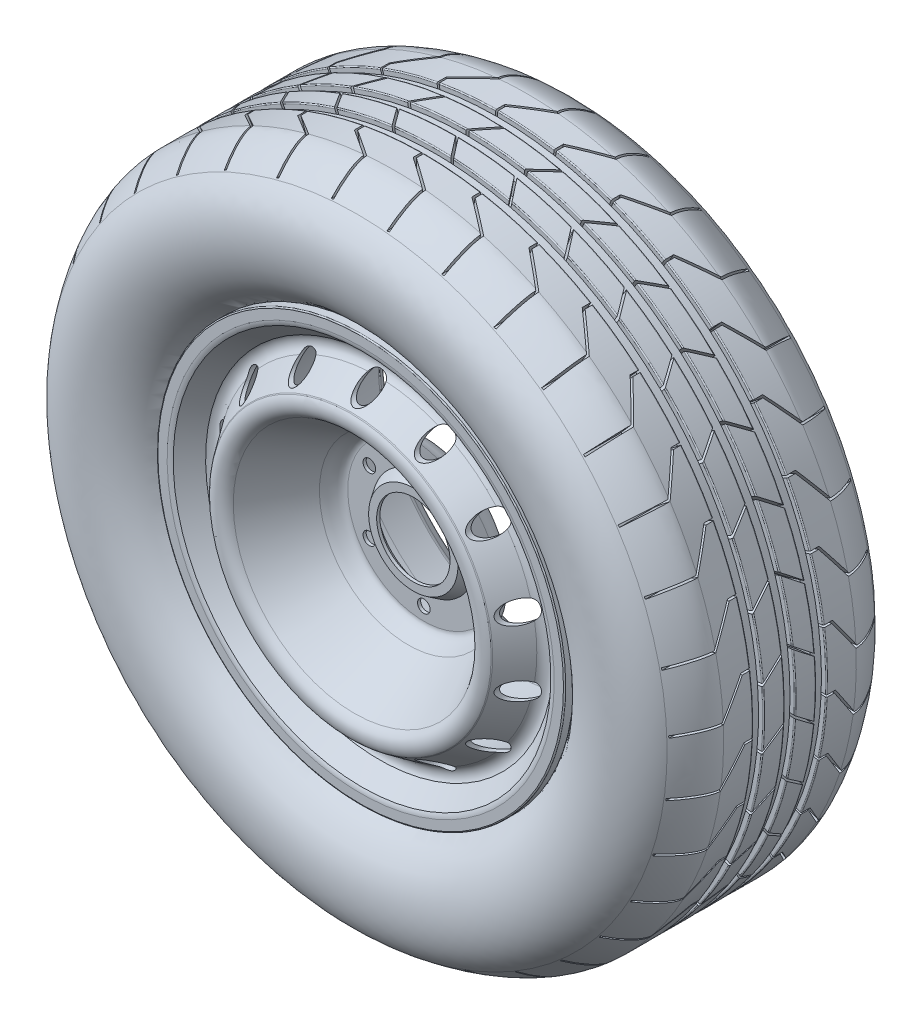
SolidWorks part; units mm, degrees
ref_plane "Front Plane" through (0, 0, 0) normal (0, 0, 1) x (1, 0, 0)
ref_plane "Top Plane" through (0, 0, 0) normal (0, 1, 0) x (1, 0, 0)
ref_plane "Right Plane" through (0, 0, 0) normal (1, 0, 0) x (0, 0, -1)
sketch "Sketch2" plane through (0, 0, 0) normal (1, 0, 0) x (0, 0, -1)
  line L0 (-102.87, 171.5) -> (-102.87, 363.226) construction
  line L1 (-172.4105, 186.5) -> (-187, 186.5)
  line L2 (-188.8982, 188.4974) -> (-188.8982, 190.3713)
  line L3 (-166.106, 313.69) -> (-39.634, 313.69)
  line L4 (-114.6838, 293.9795) -> (-91.0562, 293.9795) construction
  line L5 (-16.8418, 188.4974) -> (-16.8418, 190.3713)
  line L6 (-16.8418, 188.4974) -> (-16.8418, 190.3713)
  line L7 (-33.3295, 186.5) -> (-18.74, 186.5)
  line L8 (0.0002, 0) -> (-150.7743, 0) construction
  line L9 (-163.9409, 313.69) -> (-168.2711, 313.69) construction
  arc A0 (-16.8418, 188.4974) -> (-18.74, 186.5) centre (-18.8418, 188.4974) cw
  arc A1 (-188.8982, 188.4974) -> (-187, 186.5) centre (-186.8982, 188.4974) ccw
  arc A2 (-16.8418, 188.4974) -> (-18.74, 186.5) centre (-18.8418, 188.4974) cw
  spline S0 degree 3 poles (-188.8982, 190.3713) (-187.4149, 194.6515) (-194.521, 198.6578) (-223.7784, 223.3952) (-229.322, 273.7879) (-201.9163, 295.5639) knots 0 0 0 0 0.092594 0.175691 1 1 1 1
  spline S1 degree 3 poles (-201.9163, 295.5639) (-194.6857, 301.6028) (-177.0156, 313.69) (-166.106, 313.69) knots 0 0 0 0 1 1 1 1
  spline S2 degree 3 poles (-102.87, 293.9795) (-122.2086, 293.9795) (-146.8081, 294.4252) (-182.441, 290.3618) (-213.5532, 285.0067) (-215.3462, 259.1729) (-214.3595, 234.0884) (-206.2518, 212.706) (-194.3591, 205.2939) knots 0 0 0 0 0.276163 0.412599 0.589198 0.675863 0.783624 1 1 1 1
  spline S3 degree 3 poles (-194.3591, 205.2939) (-184.6262, 203.6803) (-171.0703, 198.8755) (-172.4105, 186.5) knots 0 0 0 0 1 1 1 1
  spline S4 degree 3 poles (-11.3809, 205.2939) (-21.1138, 203.6803) (-34.6697, 198.8755) (-33.3295, 186.5) knots 0 0 0 0 1 1 1 1
  spline S5 degree 3 poles (-102.87, 293.9795) (-83.5314, 293.9795) (-58.9319, 294.4252) (-23.299, 290.3618) (7.8132, 285.0067) (9.6062, 259.1729) (8.6195, 234.0884) (0.5118, 212.706) (-11.3809, 205.2939) knots 0 0 0 0 0.276163 0.412599 0.589198 0.675863 0.783624 1 1 1 1
  spline S6 degree 3 poles (-3.8237, 295.5639) (-11.0543, 301.6028) (-28.7244, 313.69) (-39.634, 313.69) knots 0 0 0 0 1 1 1 1
  spline S7 degree 3 poles (-16.8418, 190.3713) (-18.3251, 194.6515) (-11.219, 198.6578) (18.0384, 223.3952) (23.582, 273.7879) (-3.8237, 295.5639) knots 0 0 0 0 0.092594 0.175691 1 1 1 1
  point P47 (-102.87, 313.69)
  point P53 (-102.87, 313.69)
  dimension "D1" = 313.69
sketch "Sketch3" plane through (0, 0, 0) normal (1, 0, 0) x (0, 0, -1)
  line L0 (-264.7201, 60) -> (-86.538, 60) construction
  line L1 (0.0002, 0) -> (-150.7743, 0) construction
  line L2 (-268.006, 35) -> (-128.0931, 35) construction
  line L3 (-205.9767, 132.5457) -> (-168.3287, 158.905)
  line L4 (-202.9838, 118.0971) -> (-154.1889, 89.0608)
  line L5 (-138.325, 70.6649) -> (-138.325, 74.3351) construction
  line L6 (-204.5179, 115.519) -> (-153.0125, 84.8698)
  line L7 (-138.325, 72.5) -> (-138.325, 49.129)
  line L8 (-149.8204, 88.8687) -> (-148.4553, 97.5226) construction
  line L9 (-135.325, 72.5) -> (-135.325, 47.5)
  line L10 (-145.325, 41.0069) -> (-135.325, 47.5)
  line L11 (-148.325, 42.6359) -> (-138.325, 49.129)
  line L12 (-148.325, 35) -> (-148.325, 42.6359)
  line L13 (-148.325, 35) -> (-145.325, 35)
  line L14 (-135.325, 69.7933) -> (-135.325, 75.2068) construction
  line L15 (-207.6973, 135.0032) -> (-182.9379, 152.3386)
  line L16 (-207.6973, 135.0032) -> (-208.4087, 134.3022)
  line L17 (-207.6973, 135.0032) -> (-170.0494, 161.3625) construction
  line L18 (-152.5765, 90.65) -> (-151.4186, 97.9901) construction
  line L19 (-102.87, 171.5) -> (-102.87, 0) construction
  line L37 (-18.7062, 174.8816) -> (-18.7062, -14.0227) construction
  line L38 (-19.6768, 162.2421) -> (-50.5335, 160.6051)
  line L39 (-8.6133, 169.732) -> (-16.5029, 163.5956)
  line L40 (-3.2572, 181.7244) -> (-6.3673, 172.9513)
  line L41 (-2.4789, 190.0232) -> (-2.4789, 185.1993)
  line L50 (-145.325, 35) -> (-145.325, 41.0069)
  line L62 (-50.5335, 160.6051) -> (-168.3287, 158.905)
  line L63 (-15.8487, 193.5755) -> (-8.0026, 193.5755)
  line L64 (-16.5655, 188.0964) -> (-16.5655, 192.8587)
  line L65 (-21.0323, 177.6907) -> (-17.0667, 186.277)
  line L66 (-29.906, 169.8214) -> (-23.0413, 175.1606)
  line L67 (-60.5422, 168.7285) -> (-33.1346, 168.7285)
  line L68 (-197.2477, 180.0601) -> (-180.6139, 165.7725)
  line L69 (-198.5359, 193.3989) -> (-198.5359, 184.567)
  line L70 (-189.9573, 194.491) -> (-197.4438, 194.491)
  line L71 (-188.9775, 188.7534) -> (-188.9775, 193.5112)
  line L72 (-180.6139, 175.9717) -> (-187.2992, 184.567)
  line L73 (-177.2296, 173.7879) -> (-180.6139, 175.9717)
  line L74 (-60.5422, 168.7285) -> (-164.6364, 169.6441)
  line L75 (-138.325, 72.5) -> (-138.325, 49.129) construction
  arc A0 (-205.9767, 132.5457) -> (-202.9838, 118.0971) centre (-197.87, 126.6906) ccw
  arc A1 (-180.6139, 165.7725) -> (-182.9379, 152.3386) centre (-188.4928, 160.2175) cw
  arc A2 (-208.4087, 134.3022) -> (-204.5179, 115.519) centre (-197.87, 126.6906) ccw
  arc A4 (-205.9767, 132.5457) -> (-202.9838, 118.0971) centre (-197.87, 126.6906) ccw construction
  arc A5 (-154.1889, 89.0608) -> (-152.5765, 90.65) centre (-146.8356, 83.2127) cw construction
  arc A19 (-198.5359, 193.3989) -> (-197.4438, 194.491) centre (-197.3457, 193.3009) cw
  arc A20 (-188.9775, 193.5112) -> (-189.9573, 194.491) centre (-190.0696, 193.3989) ccw
  arc A21 (-15.8487, 193.5755) -> (-16.5655, 192.8587) centre (-15.8203, 192.8303) ccw
  arc A22 (-2.4789, 190.0232) -> (-8.0026, 193.5755) centre (-5.2407, 191.7993) ccw
  arc A23 (-29.906, 169.8214) -> (-33.1346, 168.7285) centre (-32.7758, 172.9841) cw
  arc A24 (-19.6768, 162.2421) -> (-16.5029, 163.5956) centre (-20.3064, 168.1163) ccw
  arc A31 (-198.5359, 184.567) -> (-197.2477, 180.0601) centre (-188.1081, 185.11) ccw
  arc A32 (-188.9775, 188.7534) -> (-187.2992, 184.567) centre (-182.2724, 189.0119) ccw
  arc A33 (-164.6364, 169.6441) -> (-177.2296, 173.7879) centre (-165.4833, 188.2776) cw
  arc A34 (-23.0413, 175.1606) -> (-21.0323, 177.6907) centre (-28.4573, 181.5237) ccw
  arc A35 (-16.5655, 188.0964) -> (-17.0667, 186.277) centre (-19.6313, 187.9621) cw
  arc A36 (-6.3673, 172.9513) -> (-8.6133, 169.732) centre (-12.4381, 174.7936) cw
  arc A37 (-2.4789, 185.1993) -> (-3.2572, 181.7244) centre (-8.967, 184.8279) cw
  arc A38 (-153.0125, 84.8698) -> (-149.8204, 88.8687) centre (-146.8356, 83.2127) cw construction
  spline S1 degree 3 poles (-153.0125, 84.8698) (-151.0641, 83.7104) (-144.2655, 80.5424) (-138.325, 76.2907) (-138.325, 72.5) knots 0 0 0 0 0.479313 1 1 1 1
  spline S2 degree 3 poles (-154.1889, 89.0608) (-147.1802, 84.8902) (-141.0576, 83.9707) (-135.325, 76.3082) (-135.325, 72.5) knots 0 0 0 0 0.640505 1 1 1 1
  dimension "D1" = 60
  dimension "D3" = 10
  dimension "D4" = 42.455
  dimension "D10" = 3
  dimension "D2" = 35
  dimension "D6" = 25
  dimension "D7" = 10
  dimension "D8" = 95
  dimension "D5" = 3
  dimension "D9" = 3
revolve "Revolve2" add sketch "Sketch3" angle 360 about L8
sketch "Sketch6" plane through (0, 0, 0) normal (1, 0, 0) x (0, 0, -1)
  line L0 (-102.87, 171.5) -> (-102.87, -118.6175) construction
ref_plane "Plane1" through (0, 0, 258.5359) normal (0, 0, 1) x (1, 0, 0)
sketch "Sketch4" plane through (0, 0, 258.5359) normal (0, 0, 1) x (1, 0, 0)
  circle A0 centre (0, 147) radius 10
  circle A1 centre (63.7809, 132.4424) radius 10
  circle A2 centre (114.9292, 91.653) radius 10
  circle A3 centre (143.3144, 32.7106) radius 10
  circle A4 centre (143.3144, -32.7106) radius 10
  circle A5 centre (114.9292, -91.653) radius 10
  circle A6 centre (63.7809, -132.4424) radius 10
  circle A7 centre (0, -147) radius 10
  circle A8 centre (-63.7809, -132.4424) radius 10
  circle A9 centre (-114.9292, -91.653) radius 10
  circle A10 centre (-143.3144, -32.7106) radius 10
  circle A11 centre (-143.3144, 32.7106) radius 10
  circle A12 centre (-114.9292, 91.653) radius 10
  circle A13 centre (-63.7809, 132.4424) radius 10
  point P31 (0, 0)
  dimension "D1" = 20
  dimension "D2" = 147
  dimension "D3" = 14
extrude "Cut-Extrude1" cut sketch "Sketch4" against normal blind 280
sketch "Sketch5" plane through (0, 0, 138.325) normal (0, 0, 1) x (1, 0, 0)
  circle A0 centre (0, 60) radius 6
  circle A1 centre (51.9615, 30) radius 6
  circle A2 centre (51.9615, -30) radius 6
  circle A3 centre (0, -60) radius 6
  circle A4 centre (-51.9615, -30) radius 6
  circle A5 centre (-51.9615, 30) radius 6
  point P13 (0, 0)
  dimension "D1" = 12
  dimension "D2" = 60
  dimension "D3" = 6
extrude "Cut-Extrude2" cut sketch "Sketch5" against normal through all
revolve "Revolve3" add sketch "Sketch2" angle 360 about L8 region at (0, 189.1767, 179.7052)
sketch "Sketch8" plane through (0, 0, 0) normal (1, 0, 0) x (0, 0, -1)
  line L0 (-102.87, 313.69) -> (-102.87, 255.2302) construction
  line L1 (-39.634, 313.69) -> (-166.106, 313.69) construction
  line L2 (-137.87, 308.69) -> (-127.87, 308.69)
  line L3 (-107.87, 313.69) -> (-97.87, 313.69)
  line L4 (-107.87, 313.69) -> (-107.87, 308.69)
  line L5 (-107.87, 308.69) -> (-97.87, 308.69)
  line L6 (-97.87, 313.69) -> (-97.87, 308.69)
  line L7 (-137.87, 313.69) -> (-127.87, 313.69)
  line L8 (-137.87, 313.69) -> (-137.87, 308.69)
  line L9 (-127.87, 313.69) -> (-127.87, 308.69)
  line L10 (-77.87, 308.69) -> (-67.87, 308.69)
  line L11 (-77.87, 313.69) -> (-67.87, 313.69)
  line L12 (-77.87, 313.69) -> (-77.87, 308.69)
  line L13 (-67.87, 313.69) -> (-67.87, 308.69)
  dimension "D1" = 10
  dimension "D2" = 5
  dimension "D3" = 2
  dimension "D4" = 2
revolve "Cut-Revolve1" cut sketch "Sketch8" angle 360 about axis through (0, 0, 168.3287) along (0, 0, 1)
ref_plane "Plane3" through (0, 320, 0) normal (0, 1, 0) x (1, 0, 0)
fillet "Fillet1" radius 1 6 edges at (0, 313.69, 137.87) (0, 313.69, 127.87) (0, 313.69, 107.87) (0, 313.69, 97.87) (0, 313.69, 77.87) (0, 313.69, 67.87)
sketch "Sketch9" plane through (0, 320, 0) normal (0, 1, 0) x (1, 0, 0)
  line L0 (0, -220.6296) -> (0, 14.8896) construction
  line L1 (-253.3411, -220.6296) -> (253.3411, -220.6296) construction
  line L2 (253.3411, 14.8896) -> (-253.3411, 14.8896) construction
  line L3 (0, -137.87) -> (0, -145.4463)
  line L4 (313.69, -137.87) -> (-313.69, -137.87) construction
  line L5 (0, -145.4463) -> (29.5915, -166.106)
  line L6 (313.69, -166.106) -> (-313.69, -166.106) construction
  line L7 (29.5915, -166.106) -> (29.5915, -220.6296)
  line L8 (-2, -137.87) -> (-2, -146.4892)
  line L9 (-2, -146.4892) -> (27.5915, -167.1489)
  line L10 (27.5915, -167.1489) -> (27.5915, -220.6296)
  line L11 (27.5915, -220.6296) -> (29.5915, -220.6296)
  line L12 (-2, -137.87) -> (0, -137.87)
  line L13 (-308.69, -102.87) -> (308.69, -102.87) construction
  line L14 (-308.69, -97.87) -> (-308.69, -107.87) construction
  line L15 (308.69, -107.87) -> (308.69, -97.87) construction
  line L16 (-2, -67.87) -> (0, -67.87)
  line L17 (27.5915, 14.8896) -> (29.5915, 14.8896)
  line L18 (27.5915, -38.5911) -> (27.5915, 14.8896)
  line L19 (-2, -59.2508) -> (27.5915, -38.5911)
  line L20 (-2, -67.87) -> (-2, -59.2508)
  line L21 (29.5915, -39.634) -> (29.5915, 14.8896)
  line L22 (0, -60.2937) -> (29.5915, -39.634)
  line L23 (0, -67.87) -> (0, -60.2937)
  line L24 (0, -50.5335) -> (0, -168.3287) construction
  line L25 (0, -107.87) -> (15.389, -127.87)
  line L26 (312.69, -107.87) -> (-312.69, -107.87) construction
  line L27 (-308.69, -127.87) -> (308.69, -127.87) construction
  line L28 (2.5235, -107.87) -> (17.9125, -127.87)
  line L29 (0, -107.87) -> (2.5235, -107.87)
  line L30 (15.389, -127.87) -> (17.9125, -127.87)
  line L31 (1.5851, -106.6504) -> (16.974, -126.6504) construction
  line L32 (15.389, -77.87) -> (17.9125, -77.87)
  line L33 (0, -97.87) -> (2.5235, -97.87)
  line L34 (2.5235, -97.87) -> (17.9125, -77.87)
  line L35 (0, -97.87) -> (15.389, -77.87)
  dimension "D1" = 2
  dimension "D2" = 2
extrude "Cut-Extrude3" cut sketch "Sketch9" against normal blind 25
pattern_circular "CirPattern1" count 35 over 360 about axis through (0, 0, 168.3287) along (0, 0, 1) of "Cut-Extrude3"
